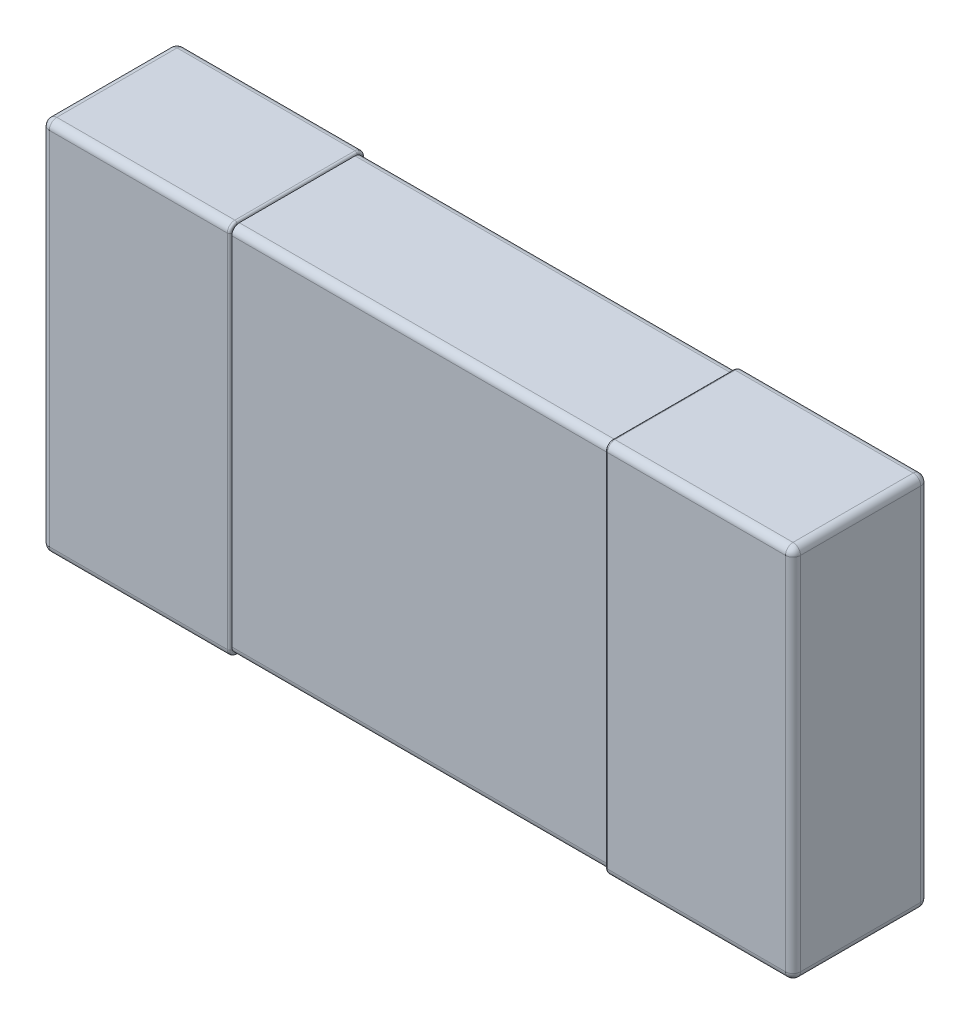
SolidWorks part; units mm, degrees
ref_plane "Top Plane" through (0, 0, 0) normal (0, 0, 1) x (1, 0, 0)
ref_plane "Front Plane" through (0, 0, 0) normal (0, 1, 0) x (1, 0, 0)
ref_plane "Side Plane" through (0, 0, 0) normal (1, 0, 0) x (0, 0, -1)
sketch "Sketch1" plane through (0, 0, 0) normal (0, 0, 1) x (1, 0, 0)
  line L1 (-0.5, 0.25) -> (0.5, 0.25)
  line L2 (-0.5, 0.25) -> (-0.5, -0.25)
  line L3 (-0.5, -0.25) -> (0.5, -0.25)
  line L4 (0.5, 0.25) -> (0.5, -0.25)
  dimension "D1" = 1
  dimension "D2" = 0.5
  dimension "D3" = 0.5
  dimension "D4" = 0.25
extrude "All body" add sketch "Sketch1" along normal blind 0.18
sketch "Sketch2" plane through (0, 0, 0) normal (1, 0, 0) x (0, 0, -1)
  line L14 (-0.003, 0.247) -> (-0.177, 0.247)
  line L15 (-0.003, -0.247) -> (-0.003, 0.247)
  line L16 (-0.177, -0.247) -> (-0.003, -0.247)
  line L17 (-0.177, 0.247) -> (-0.177, -0.247)
  line L18 (-0.003, 0.247) -> (-0.177, 0.247)
  line L19 (-0.003, -0.247) -> (-0.003, 0.247)
  line L20 (-0.177, -0.247) -> (-0.003, -0.247)
  line L21 (-0.177, 0.247) -> (-0.177, -0.247)
  dimension "D1" = 0.003
extrude "Cut out the body for pin" cut sketch "Sketch2" against normal blind 0.25 and the other way blind 0.25 flip side to cut
fillet "Body fillet" radius 0.01 4 edges at (0, 0.247, 0.003) (0, 0.247, 0.177) (0, -0.247, 0.003) (0, -0.247, 0.177)
fillet "Pin fillet a" radius 0.01 16 edges at (0.5, -0.25, 0.09) (0.5, 0, 0.18) (0.5, 0.25, 0.09) (0.5, 0, 0) (-0.5, 0.25, 0.09) (-0.5, 0, 0.18) (-0.5, -0.25, 0.09) (-0.5, 0, 0) (0.375, 0.25, 0.18) (0.375, -0.25, 0.18) (0.375, -0.25, 0) (0.375, 0.25, 0) (-0.375, 0.25, 0) (-0.375, -0.25, 0) (-0.375, 0.25, 0.18) (-0.375, -0.25, 0.18)
fillet "Pin fillet b" radius 0.003 16 edges at (0.25, -0.2471, 0.1771) (0.25, -0.25, 0.09) (0.25, -0.2471, 0.0029) (0.25, 0, 0) (0.25, 0.2471, 0.0029) (0.25, 0.25, 0.09) (0.25, 0.2471, 0.1771) (-0.25, -0.2471, 0.1771) (-0.25, -0.25, 0.09) (-0.25, -0.2471, 0.0029) (-0.25, 0, 0) (-0.25, 0.2471, 0.0029) (-0.25, 0.25, 0.09) (-0.25, 0.2471, 0.1771) (0.25, 0, 0.18) (-0.25, 0, 0.18)
